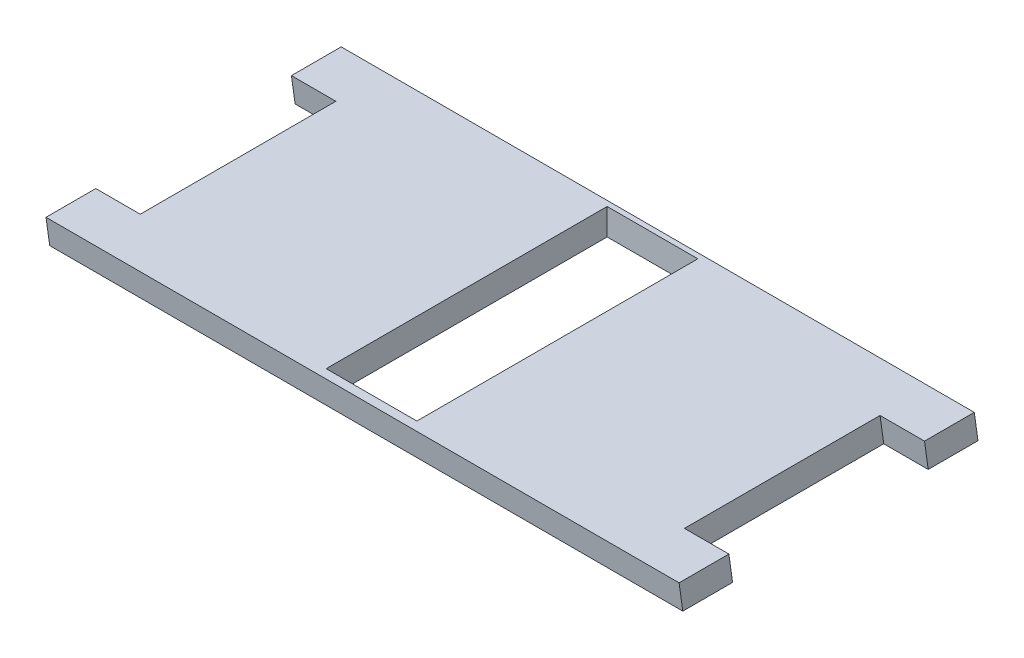
SolidWorks part; units mm, degrees
material "Balsa"
ref_plane "Front Plane" through (0, 0, 0) normal (0, 0, 1) x (1, 0, 0)
ref_plane "Top Plane" through (0, 0, 0) normal (0, 1, 0) x (1, 0, 0)
ref_plane "Right Plane" through (0, 0, 0) normal (1, 0, 0) x (0, 0, -1)
sketch "Sketch1" plane through (0, 0, 0) normal (0, 1, 0) x (1, 0, 0)
  line L3 (90.424, 0) -> (0, 0)
  line L4 (0, 0) -> (0, 7.112) construction
  line L5 (0, 7.112) -> (6.35, 7.112)
  line L6 (6.35, 7.112) -> (6.35, 35.052)
  line L7 (6.35, 35.052) -> (0, 35.052)
  line L8 (0, 7.112) -> (0, 0)
  line L10 (6.35, 7.112) -> (84.074, 7.112) construction
  line L11 (84.074, 7.112) -> (90.424, 7.112)
  line L12 (84.074, 7.112) -> (84.074, 35.052)
  line L13 (84.074, 35.052) -> (90.424, 35.052)
  line L15 (90.424, 7.112) -> (90.424, 0)
  line L16 (0, 35.052) -> (0, 42.164)
  line L17 (0, 42.164) -> (90.424, 42.164)
  line L18 (90.424, 42.164) -> (90.424, 35.052)
  dimension "D1" = 7.112
  dimension "D2" = 90.424
  dimension "D3" = 6.35
  dimension "D4" = 27.94
  dimension "D5" = 77.724
  dimension "D6" = 6.35
  dimension "D7" = 27.94
  dimension "D8" = 7.112
ref_plane "Plane1" through (0, 3.7729, 0) normal (0, 1, 0) x (1, 0, 0)
sketch "Sketch2" plane through (0, 3.7729, 0) normal (0, 1, 0) x (1, 0, 0)
  line L0 (0, 0) -> (0, -0.5302) construction
  line L1 (0, -0.5302) -> (90.424, -0.5302)
  line L2 (90.424, -0.5302) -> (90.424, 6.5818)
  line L3 (90.424, 7.112) -> (90.424, 0) construction
  line L4 (90.424, 6.5818) -> (84.074, 6.5818)
  line L5 (84.074, 6.5818) -> (84.074, 34.5218)
  line L6 (84.074, 7.112) -> (84.074, 35.052) construction
  line L7 (84.074, 34.5218) -> (90.424, 34.5218)
  line L8 (90.424, 34.5218) -> (90.424, 41.6338)
  line L9 (90.424, 42.164) -> (90.424, 35.052) construction
  line L10 (90.424, 41.6338) -> (0, 41.6338)
  line L11 (0, 35.052) -> (0, 42.164) construction
  line L12 (0, 41.6338) -> (0, 34.5218)
  line L13 (0, 34.5218) -> (6.35, 34.5218)
  line L14 (6.35, 7.112) -> (6.35, 35.052) construction
  line L15 (6.35, 34.5218) -> (6.35, 6.5818)
  line L16 (6.35, 6.5818) -> (0, 6.5818)
  line L17 (0, 7.112) -> (0, 0) construction
  line L18 (0, 6.5818) -> (0, -0.5302)
  dimension "D1" = 0.5302
  dimension "D2" = 90.424
  dimension "D3" = 7.112
  dimension "D4" = 6.35
  dimension "D5" = 27.94
  dimension "D6" = 6.35
  dimension "D7" = 7.112
  dimension "D8" = 90.424
  dimension "D9" = 7.112
  dimension "D10" = 6.35
  dimension "D11" = 27.94
  dimension "D12" = 6.35
  dimension "D13" = 7.112
loft "Loft1" add profiles "Sketch1", "Sketch2" connector at (6.35, 0, -7.112) connector at (6.35, 3.7729, -6.5818)
sketch "Sketch3" plane through (0, 3.7729, 0) normal (0, 1, 0) x (1, 0, 0)
  line L0 (0, 0) -> (90.424, 0) construction
  line L1 (90.424, -0.5302) -> (90.424, 6.5818) construction
  line L2 (45.212, 0) -> (45.212, 41.6338) construction
  line L3 (90.424, 41.6338) -> (0, 41.6338) construction
  line L5 (51.689, 0.7509) -> (38.735, 0.7509)
  line L6 (51.689, 0.7509) -> (51.689, 40.8829)
  line L7 (51.689, 40.8829) -> (38.735, 40.8829)
  line L8 (38.735, 0.7509) -> (38.735, 40.8829)
  line L9 (51.689, 0.7509) -> (38.735, 40.8829) construction
  line L10 (51.689, 40.8829) -> (38.735, 0.7509) construction
  point P9 (45.212, 20.8169)
  dimension "D1" = 90.424
  dimension "D2" = 41.6338
  dimension "D3" = 40.132
  dimension "D4" = 12.954
extrude "Cut-Extrude1" cut sketch "Sketch3" against normal blind 12.7
